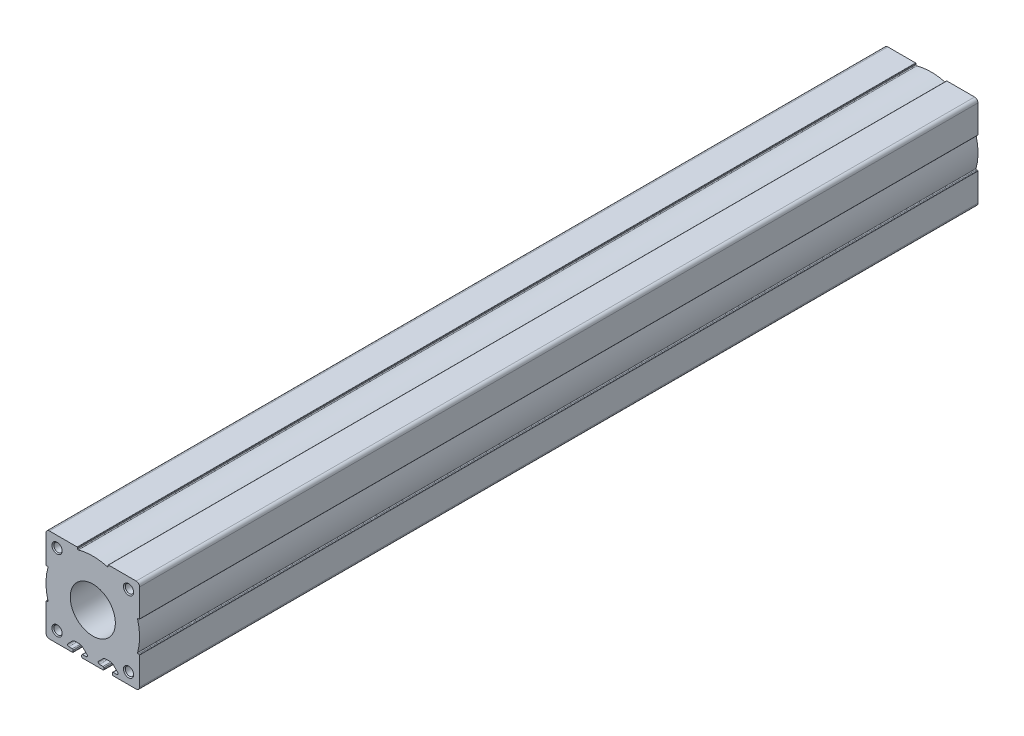
SolidWorks part; units mm, degrees
ref_plane "Front Plane" through (0, 0, 0) normal (0, 0, 1) x (1, 0, 0)
ref_plane "Top Plane" through (0, 0, 0) normal (0, 1, 0) x (1, 0, 0)
ref_plane "Right Plane" through (0, 0, 0) normal (1, 0, 0) x (0, 0, -1)
sketch "Sketch1" plane through (0, 0, 0) normal (0, 0, 1) x (1, 0, 0)
  line L0 (-25.5, -27.5) -> (25.5, -27.5)
  line L1 (27.5, -25.5) -> (27.5, 25.5)
  line L2 (25.5, 27.5) -> (-25.5, 27.5)
  line L3 (-27.5, 25.5) -> (-27.5, -25.5)
  arc A0 (-27.5, -25.5) -> (-25.5, -27.5) centre (-25.5, -25.5) ccw
  arc A1 (25.5, -27.5) -> (27.5, -25.5) centre (25.5, -25.5) ccw
  arc A2 (27.5, 25.5) -> (25.5, 27.5) centre (25.5, 25.5) ccw
  arc A3 (-25.5, 27.5) -> (-27.5, 25.5) centre (-25.5, 25.5) ccw
extrude "Boss-Extrude1" add sketch "Sketch1" against normal blind 492.7
sketch "Sketch2" plane through (0, 0, 0) normal (0, 0, 1) x (1, 0, 0)
  line L0 (-55, -55) -> (55, -55)
  line L1 (55, -55) -> (55, 55)
  line L2 (55, 55) -> (-55, 55)
  line L3 (-55, 55) -> (-55, -55)
  line L4 (-26.6993, -9) -> (-27.3, -9)
  line L5 (-27.5, -9.2) -> (-27.5, -25.5)
  line L6 (-25.5, -27.5) -> (-11.75, -27.5)
  line L7 (-11.75, -27.5) -> (-11.6464, -27.3964)
  line L8 (-11.5, -27.0429) -> (-11.5, -26.2)
  line L9 (-12, -25.7) -> (-14.0893, -25.7)
  line L10 (-14.6197, -24.4197) -> (-12.1787, -21.9787)
  line L11 (-10.0574, -21.1) -> (-7.9426, -21.1)
  line L12 (-5.8213, -21.9787) -> (-3.3803, -24.4197)
  line L13 (-3.9107, -25.7) -> (-6, -25.7)
  line L14 (-6.5, -26.2) -> (-6.5, -27.0429)
  line L15 (-6.3536, -27.3964) -> (-6.25, -27.5)
  line L16 (-6.25, -27.5) -> (6.25, -27.5)
  line L17 (6.25, -27.5) -> (6.3536, -27.3964)
  line L18 (6.5, -27.0429) -> (6.5, -26.2)
  line L19 (6, -25.7) -> (3.9107, -25.7)
  line L20 (3.3803, -24.4197) -> (5.8213, -21.9787)
  line L21 (7.9426, -21.1) -> (10.0574, -21.1)
  line L22 (12.1787, -21.9787) -> (14.6197, -24.4197)
  line L23 (14.0893, -25.7) -> (12, -25.7)
  line L24 (11.5, -26.2) -> (11.5, -27.0429)
  line L25 (11.6464, -27.3964) -> (11.75, -27.5)
  line L26 (11.75, -27.5) -> (25.5, -27.5)
  line L27 (27.5, -25.5) -> (27.5, -9.2)
  line L28 (27.3, -9) -> (26.6993, -9)
  line L29 (26.6993, 9) -> (27.3, 9)
  line L30 (27.5, 9.2) -> (27.5, 25.5)
  line L31 (25.5, 27.5) -> (9.2, 27.5)
  line L32 (9, 27.3) -> (9, 26.6993)
  line L33 (-9, 26.6993) -> (-9, 27.3)
  line L34 (-9.2, 27.5) -> (-25.5, 27.5)
  line L35 (-27.5, 25.5) -> (-27.5, 9.2)
  line L36 (-27.3, 9) -> (-26.6993, 9)
  arc A0 (-26.3146, 8.4904) -> (-26.3146, -8.4904) centre (3.5, 0) ccw
  arc A1 (-26.3146, -8.4904) -> (-26.6993, -9) centre (-26.6993, -8.6) cw
  arc A2 (-27.3, -9) -> (-27.5, -9.2) centre (-27.3, -9.2) ccw
  arc A3 (-27.5, -25.5) -> (-25.5, -27.5) centre (-25.5, -25.5) ccw
  arc A4 (-11.6464, -27.3964) -> (-11.5, -27.0429) centre (-12, -27.0429) ccw
  arc A5 (-11.5, -26.2) -> (-12, -25.7) centre (-12, -26.2) ccw
  arc A6 (-14.0893, -25.7) -> (-14.6197, -24.4197) centre (-14.0893, -24.95) cw
  arc A7 (-12.1787, -21.9787) -> (-10.0574, -21.1) centre (-10.0574, -24.1) cw
  arc A8 (-7.9426, -21.1) -> (-5.8213, -21.9787) centre (-7.9426, -24.1) cw
  arc A9 (-3.3803, -24.4197) -> (-3.9107, -25.7) centre (-3.9107, -24.95) cw
  arc A10 (-6, -25.7) -> (-6.5, -26.2) centre (-6, -26.2) ccw
  arc A11 (-6.5, -27.0429) -> (-6.3536, -27.3964) centre (-6, -27.0429) ccw
  arc A12 (6.3536, -27.3964) -> (6.5, -27.0429) centre (6, -27.0429) ccw
  arc A13 (6.5, -26.2) -> (6, -25.7) centre (6, -26.2) ccw
  arc A14 (3.9107, -25.7) -> (3.3803, -24.4197) centre (3.9107, -24.95) cw
  arc A15 (5.8213, -21.9787) -> (7.9426, -21.1) centre (7.9426, -24.1) cw
  arc A16 (10.0574, -21.1) -> (12.1787, -21.9787) centre (10.0574, -24.1) cw
  arc A17 (14.6197, -24.4197) -> (14.0893, -25.7) centre (14.0893, -24.95) cw
  arc A18 (12, -25.7) -> (11.5, -26.2) centre (12, -26.2) ccw
  arc A19 (11.5, -27.0429) -> (11.6464, -27.3964) centre (12, -27.0429) ccw
  arc A20 (25.5, -27.5) -> (27.5, -25.5) centre (25.5, -25.5) ccw
  arc A21 (27.5, -9.2) -> (27.3, -9) centre (27.3, -9.2) ccw
  arc A22 (26.6993, -9) -> (26.3146, -8.4904) centre (26.6993, -8.6) cw
  arc A23 (26.3146, -8.4904) -> (26.3146, 8.4904) centre (-3.5, 0) ccw
  arc A24 (26.3146, 8.4904) -> (26.6993, 9) centre (26.6993, 8.6) cw
  arc A25 (27.3, 9) -> (27.5, 9.2) centre (27.3, 9.2) ccw
  arc A26 (27.5, 25.5) -> (25.5, 27.5) centre (25.5, 25.5) ccw
  arc A27 (9.2, 27.5) -> (9, 27.3) centre (9.2, 27.3) ccw
  arc A28 (9, 26.6993) -> (8.4904, 26.3146) centre (8.6, 26.6993) cw
  arc A29 (8.4904, 26.3146) -> (-8.4904, 26.3146) centre (0, -3.5) ccw
  arc A30 (-8.4904, 26.3146) -> (-9, 26.6993) centre (-8.6, 26.6993) cw
  arc A31 (-9, 27.3) -> (-9.2, 27.5) centre (-9.2, 27.3) ccw
  arc A32 (-25.5, 27.5) -> (-27.5, 25.5) centre (-25.5, 25.5) ccw
  arc A33 (-27.5, 9.2) -> (-27.3, 9) centre (-27.3, 9.2) ccw
  arc A34 (-26.6993, 9) -> (-26.3146, 8.4904) centre (-26.6993, 8.6) cw
extrude "Cut-Extrude1" cut sketch "Sketch2" against normal blind 492.7
ref_plane "Plane1" through (0, 0, -425) normal (0, 0, 1) x (1, 0, 0)
ref_plane "Plane2" through (-23.57, 0, 0) normal (1, 0, 0) x (0, 0, -1)
ref_plane "Plane3" through (23.57, 0, 0) normal (1, 0, 0) x (0, 0, -1)
sketch "Sketch3" plane through (0, 0, 0) normal (1, 0, 0) x (0, 0, -1)
  line L0 (478.5, 0) -> (478.5, 3.175)
  line L1 (478.5, 3.175) -> (488.5, 3.175)
  line L2 (488.5, 3.175) -> (488.5, 9.8)
  line L3 (488.5, 9.8) -> (488.3, 10)
  line L4 (488.3, 10) -> (478.5, 10)
  line L5 (478.5, 10) -> (478.5, 14)
  line L6 (478.5, 14) -> (490.2, 14)
  line L7 (490.2, 14) -> (490.2, 19.0625)
  line L8 (490.2, 19.0625) -> (492.7, 19.0625)
  line L9 (492.7, 19.0625) -> (492.7, 0)
  line L10 (492.7, 0) -> (478.5, 0)
  line L11 (492.7, 0) -> (478.5, 0) construction
revolve "Cut-Revolve1" cut sketch "Sketch3" angle 360 about L11 reverse direction yes
sketch "Sketch4" plane through (0, 0, 0) normal (1, 0, 0) x (0, 0, -1)
  line L0 (-21.5, 0) -> (-21.5, 13.26)
  line L1 (-21.5, 13.26) -> (105, 13.26)
  line L2 (105, 13.26) -> (105, 20)
  line L3 (105, 20) -> (415, 20)
  line L4 (415, 20) -> (415, 0)
  line L5 (415, 0) -> (-21.5, 0)
  line L6 (415, 0) -> (-21.5, 0) construction
revolve "Cut-Revolve2" cut sketch "Sketch4" angle 360 about L6 reverse direction yes
ref_plane "Plane4" through (21, 0, 0) normal (1, 0, 0) x (0, 0, -1)
ref_plane "Plane5" through (-21, 0, 0) normal (1, 0, 0) x (0, 0, -1)
sketch "Sketch5" plane through (21, 0, 0) normal (1, 0, 0) x (0, 0, -1)
  line L0 (0, 21) -> (0, 24)
  line L1 (0, 24) -> (0.5415, 23.4585)
  line L2 (0.5415, 23.4585) -> (16, 23.4585)
  line L3 (16, 23.4585) -> (17.4194, 21)
  line L4 (17.4194, 21) -> (0, 21)
  line L5 (17.4194, 21) -> (0, 21) construction
revolve "Cut-Revolve3" cut sketch "Sketch5" angle 360 about L5 reverse direction yes
cosmetic thread "Cosmetic Thread1" parameters "D1"=14, "D2"=6
sketch "Sketch6" plane through (21, 0, 0) normal (1, 0, 0) x (0, 0, -1)
  line L0 (0, -21) -> (0, -18)
  line L1 (0, -18) -> (0.5415, -18.5415)
  line L2 (0.5415, -18.5415) -> (16, -18.5415)
  line L3 (16, -18.5415) -> (17.4194, -21)
  line L4 (17.4194, -21) -> (0, -21)
  line L5 (17.4194, -21) -> (0, -21) construction
revolve "Cut-Revolve4" cut sketch "Sketch6" angle 360 about L5 reverse direction yes
cosmetic thread "Cosmetic Thread2" parameters "D1"=14, "D2"=6
sketch "Sketch7" plane through (-21, 0, 0) normal (1, 0, 0) x (0, 0, -1)
  line L0 (0, 21) -> (0, 24)
  line L1 (0, 24) -> (0.5415, 23.4585)
  line L2 (0.5415, 23.4585) -> (16, 23.4585)
  line L3 (16, 23.4585) -> (17.4194, 21)
  line L4 (17.4194, 21) -> (0, 21)
  line L5 (17.4194, 21) -> (0, 21) construction
revolve "Cut-Revolve5" cut sketch "Sketch7" angle 360 about L5 reverse direction yes
cosmetic thread "Cosmetic Thread3" parameters "D1"=14, "D2"=6
sketch "Sketch8" plane through (-21, 0, 0) normal (1, 0, 0) x (0, 0, -1)
  line L0 (0, -21) -> (0, -18)
  line L1 (0, -18) -> (0.5415, -18.5415)
  line L2 (0.5415, -18.5415) -> (16, -18.5415)
  line L3 (16, -18.5415) -> (17.4194, -21)
  line L4 (17.4194, -21) -> (0, -21)
  line L5 (17.4194, -21) -> (0, -21) construction
revolve "Cut-Revolve6" cut sketch "Sketch8" angle 360 about L5 reverse direction yes
cosmetic thread "Cosmetic Thread4" parameters "D1"=14, "D2"=6
sketch "Sketch9" plane through (-23.57, 0, 0) normal (1, 0, 0) x (0, 0, -1)
  line L0 (476.5066, 23.57) -> (477.7, 25.637)
  line L1 (477.7, 25.637) -> (492.267, 25.637)
  line L2 (492.267, 25.637) -> (492.7, 26.07)
  line L3 (492.7, 26.07) -> (492.7, 23.57)
  line L4 (492.7, 23.57) -> (476.5066, 23.57)
  line L5 (492.7, 23.57) -> (476.5066, 23.57) construction
revolve "Cut-Revolve7" cut sketch "Sketch9" angle 360 about L5 reverse direction yes
cosmetic thread "Cosmetic Thread5" parameters "D1"=10, "D2"=5
sketch "Sketch10" plane through (-23.57, 0, 0) normal (1, 0, 0) x (0, 0, -1)
  line L0 (476.5066, -23.57) -> (477.7, -21.503)
  line L1 (477.7, -21.503) -> (492.267, -21.503)
  line L2 (492.267, -21.503) -> (492.7, -21.07)
  line L3 (492.7, -21.07) -> (492.7, -23.57)
  line L4 (492.7, -23.57) -> (476.5066, -23.57)
  line L5 (492.7, -23.57) -> (476.5066, -23.57) construction
revolve "Cut-Revolve8" cut sketch "Sketch10" angle 360 about L5 reverse direction yes
cosmetic thread "Cosmetic Thread6" parameters "D1"=10, "D2"=5
sketch "Sketch11" plane through (23.57, 0, 0) normal (1, 0, 0) x (0, 0, -1)
  line L0 (476.5066, 23.57) -> (477.7, 25.637)
  line L1 (477.7, 25.637) -> (492.267, 25.637)
  line L2 (492.267, 25.637) -> (492.7, 26.07)
  line L3 (492.7, 26.07) -> (492.7, 23.57)
  line L4 (492.7, 23.57) -> (476.5066, 23.57)
  line L5 (492.7, 23.57) -> (476.5066, 23.57) construction
revolve "Cut-Revolve9" cut sketch "Sketch11" angle 360 about L5 reverse direction yes
cosmetic thread "Cosmetic Thread7" parameters "D1"=10, "D2"=5
sketch "Sketch12" plane through (23.57, 0, 0) normal (1, 0, 0) x (0, 0, -1)
  line L0 (476.5066, -23.57) -> (477.7, -21.503)
  line L1 (477.7, -21.503) -> (492.267, -21.503)
  line L2 (492.267, -21.503) -> (492.7, -21.07)
  line L3 (492.7, -21.07) -> (492.7, -23.57)
  line L4 (492.7, -23.57) -> (476.5066, -23.57)
  line L5 (492.7, -23.57) -> (476.5066, -23.57) construction
revolve "Cut-Revolve10" cut sketch "Sketch12" angle 360 about L5 reverse direction yes
cosmetic thread "Cosmetic Thread8" parameters "D1"=10, "D2"=5
ref_plane "Plane6" through (0, 0, 0) normal (0, 0, 1) x (1, 0, 0)
ref_plane "Plane7" through (0, 0, -492.7) normal (0, 0, 1) x (1, 0, 0)
ref_plane "ANBAU XY" through (0, 0, 0) normal (0, 0, -1) x (-1, 0, 0)
ref_plane "ANBAU XZ" through (0, 0, 0) normal (0, 1, 0) x (1, 0, 0)
ref_plane "ANBAU YZ" through (0, 0, 0) normal (1, 0, 0) x (0, 0, -1)
ref_axis "ANBAU X" through (-80.9, 0, 0) along (1, 0, 0)
ref_axis "ANBAU Y" through (0, 50, 0) along (0, -1, 0)
ref_axis "ANBAU Z" through (0, 0, -80.9) along (0, 0, 1)
sketch3d "ANBAU"
  point P0 (0, 0, 0)
ref_plane "DIM_H2_2 XY" through (0, 0, 0) normal (0, 0, 1) x (1, 0, 0)
ref_plane "DIM_H2_2 XZ" through (0, -27.5, 0) normal (0, -1, 0) x (-1, 0, 0)
ref_plane "DIM_H2_2 YZ" through (25.5, 0, 0) normal (1, 0, 0) x (0, 0, -1)
ref_axis "DIM_H2_2 X" through (-80.9, -27.5, 0) along (1, 0, 0)
ref_axis "DIM_H2_2 Y" through (25.5, -50, 0) along (0, 1, 0)
ref_axis "DIM_H2_2 Z" through (25.5, -27.5, 80.9) along (0, 0, -1)
sketch3d "DIM_H2_2"
  point P0 (25.5, -27.5, 0)
ref_plane "TO_KS XY" through (0, 0, 0) normal (0, 0, 1) x (1, 0, 0)
ref_plane "TO_KS XZ" through (0, 0, 0) normal (0, -1, 0) x (-1, 0, 0)
ref_plane "TO_KS YZ" through (0, 0, 0) normal (1, 0, 0) x (0, 0, -1)
ref_axis "TO_KS X" through (-80.9, 0, 0) along (1, 0, 0)
ref_axis "TO_KS Y" through (0, -50, 0) along (0, 1, 0)
ref_axis "TO_KS Z" through (0, 0, 80.9) along (0, 0, -1)
sketch3d "TO_KS"
  point P0 (0, 0, 0)
ref_plane "TO_MOTOR XY" through (0, 0, -492.7) normal (0, 0, 1) x (1, 0, 0)
ref_plane "TO_MOTOR XZ" through (0, 0, 0) normal (0, -1, 0) x (-1, 0, 0)
ref_plane "TO_MOTOR YZ" through (0, 0, 0) normal (1, 0, 0) x (0, 0, -1)
ref_axis "TO_MOTOR X" through (-80.9, 0, -492.7) along (1, 0, 0)
ref_axis "TO_MOTOR Y" through (0, -50, -492.7) along (0, 1, 0)
ref_axis "TO_MOTOR Z" through (0, 0, 80.9) along (0, 0, -1)
sketch3d "TO_MOTOR"
  point P0 (0, 0, -492.7)
other "Freeze***"
